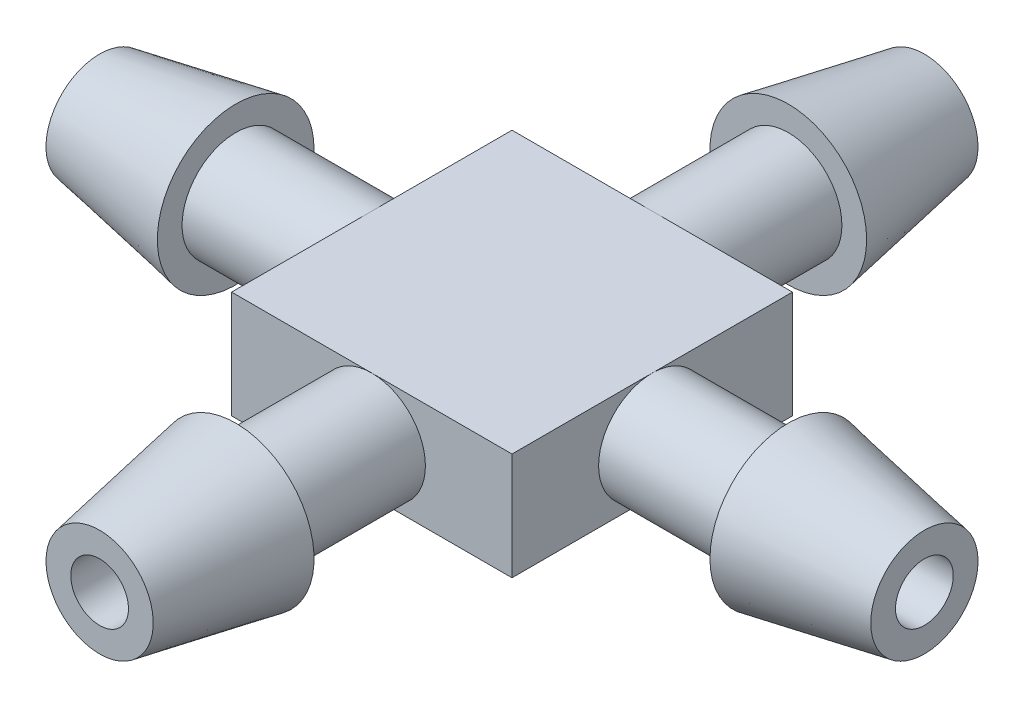
SolidWorks part; units mm, degrees
ref_plane "Płaszczyzna przednia" through (0, 0, 0) normal (0, 0, 1) x (1, 0, 0)
ref_plane "Płaszczyzna górna" through (0, 0, 0) normal (0, 1, 0) x (1, 0, 0)
ref_plane "Płaszczyzna prawa" through (0, 0, 0) normal (1, 0, 0) x (0, 0, -1)
sketch "Sketch1" plane through (0, 0, 0) normal (0, 0, 1) x (1, 0, 0)
  line L0 (-4.7909, -0.1623) -> (6.2745, -0.1623)
  line L1 (7.7664, 1.1377) -> (4.4664, 1.7377)
  line L2 (4.4664, 1.7377) -> (4.4664, 1.1377)
  line L3 (4.4664, 1.1377) -> (1.1664, 1.1377)
  line L4 (7.7664, 1.1377) -> (7.7664, 0.5377)
  line L5 (7.7664, 0.5377) -> (1.1664, 0.5377)
  line L6 (1.1664, 0.5377) -> (1.1664, 1.1377)
  dimension "D1" = 0.7
  dimension "D2" = 1.3
  dimension "D3" = 1.9
  dimension "D4" = 1.3
  dimension "D5" = 6.6
  dimension "D6" = 3.3
revolve "Revolve2" add sketch "Sketch1" angle 360 about L0 region at (4.6864, 0.9377, 0)
sketch "Sketch2" plane through (1.1664, 0, 0) normal (-1, 0, 0) x (0, 0, 1)
  line L4 (0, 1.1377) -> (0, -1.4623)
  line L5 (3.4, 1.1377) -> (3.4, -1.4623)
  line L6 (3.4, -1.4623) -> (-3.4, -1.4623)
  line L7 (-3.4, -1.4623) -> (-3.4, 1.1377)
  line L8 (-3.4, 1.1377) -> (3.4, 1.1377)
  circle A6 centre (0, -0.1623) radius 1.3 construction
  circle A7 centre (0, -0.1623) radius 1.3 construction
  circle A8 centre (0, -0.1623) radius 0.7
  circle M5 centre (0, -0.1623) radius 1.3
  circle M6 centre (0, -0.1623) radius 0.7
  dimension "D2" = 3.4
  dimension "D3" = 2.6
  dimension "D4" = 1.4
  dimension "D1" = 6.8
extrude "Boss-Extrude1" add sketch "Sketch2" along normal blind 6.8 separate body contours L8 L6 L5 M5 | L8 L7 L6 M5 | L4 M5 M6 | L4 M5 M6 region at (1.1664, 0.7364, 0.8987) region at (1.1664, -0.1623, -2.1928) region at (1.1664, -0.1623, 2.1928) region at (1.1664, 0.8377, -0.0291)
ref_plane "Plane1" through (0, 0, 0) normal (0, 0, 1) x (1, 0, 0)
ref_plane "Plane2" through (-2.2336, 0, 0) normal (-1, 0, 0) x (0, 0, 1)
ref_axis "Axis1" through (-2.2336, 1.2677, 0) along (0, -1, 0)
pattern_circular "CirPattern2" count 4 over 360 about axis through (-2.2336, 1.2677, 0) along (0, -1, 0) of "Revolve2"
sketch "Sketch3" plane through (0, 0, -10) normal (0, 0, -1) x (-1, 0, 0)
  circle A0 centre (2.2336, -0.1623) radius 0.7
  dimension "D1" = 1.4
extrude "Cut-Extrude1" cut sketch "Sketch3" against normal through all
